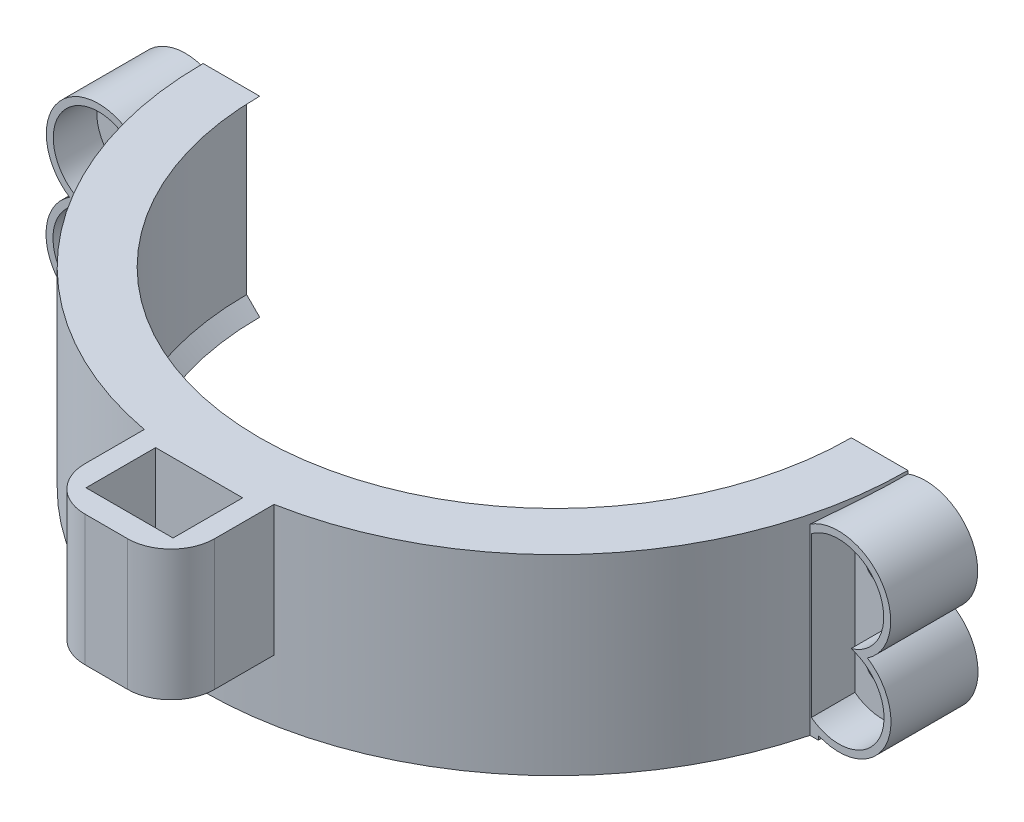
SolidWorks part; units mm, degrees
material "ABS PC"
ref_plane "Front Plane" through (0, 0, 0) normal (0, 0, 1) x (1, 0, 0)
ref_plane "Top Plane" through (0, 0, 0) normal (0, 1, 0) x (1, 0, 0)
ref_plane "Right Plane" through (0, 0, 0) normal (1, 0, 0) x (0, 0, -1)
sketch "Sketch2" plane through (0, 0, 0) normal (1, 0, 0) x (0, 0, -1)
  line L0 (0, 0) -> (-40.5, 0) construction
  line L1 (0, 0) -> (0, 11) construction
  line L24 (-34, -11) -> (-35.5, -9.5)
  line L25 (-35.5, -11) -> (-34, -11)
  line L26 (-40.5, -11) -> (-35.5, -11)
  line L27 (-40.5, 11) -> (-40.5, -11)
  line L28 (-35.5, 9.5) -> (-34, 11)
  line L29 (-35.5, -9.5) -> (-35.5, 9.5)
  line L30 (-34, 11) -> (-35.5, 11)
  line L31 (-35.5, 11) -> (-40.5, 11)
  dimension "D1" = 22
  dimension "D2" = 19
  dimension "D3" = 6.5
  dimension "D4" = 1.5
  dimension "D5" = 1.5
  dimension "D6" = 40.5
revolve "Revolve1" add sketch "Sketch2" angle 180 mid plane about L1
sketch "Sketch3" plane through (0, 0, 0) normal (0, 1, 0) x (1, 0, 0)
  line L0 (0, 0) -> (0, -51.3604) construction
  arc A2 (-40.5, 0) -> (40.5, 0) centre (0, 0) ccw
  arc A3 (-40.5, 0) -> (40.5, 0) centre (0, 0) ccw
  spline S0 degree 3 poles (40.5, 0) (41.5749, -20.6798) (31.8611, -51.1108) (0, -51.3604) knots 0 0 0 0 1 1 1 1
  spline S1 degree 3 poles (-40.5, 0) (-41.5749, -20.6798) (-31.8611, -51.1108) (0, -51.3604) knots 0 0 0 0 1 1 1 1
  dimension "D1" = 0
extrude "Boss-Extrude1" add sketch "Sketch3" against normal up to surface (11 mm away)
sketch "Sketch5" plane through (0, 0, 0) normal (0, 1, 0) x (1, 0, 0)
  line L0 (32.2986, -50) -> (-32.2986, -50)
  line L1 (0, -50) -> (0, 0) construction
  line L2 (32.2986, -50) -> (-4.5209, -70.7981)
  line L3 (-4.5209, -70.7981) -> (-32.2986, -50)
  dimension "D1" = 50
extrude "Cut-Extrude1" cut sketch "Sketch5" against normal up to next
sketch "Sketch6" plane through (0, 0, 50) normal (0, 0, 1) x (1, 0, 0)
  line L0 (-10.6698, -11) -> (10.6698, -11) construction
  line L1 (12.7, -11) -> (-12.7, -11)
  line L2 (12.7, -11) -> (12.7, 7)
  line L3 (12.7, 7) -> (-12.7, 7)
  line L4 (-12.7, -11) -> (-12.7, 7)
  line L5 (12.7, -11) -> (-12.7, 7) construction
  line L6 (12.7, 7) -> (-12.7, -11) construction
  point P0 (0, -2)
  dimension "D1" = 25.4
  dimension "D2" = 18
extrude "Boss-Extrude2" add sketch "Sketch6" against normal up to surface and the other way blind 15 up to face at (10.125, 8.25, 10.125)
sketch "Sketch8" plane through (0, 11, 0) normal (0, 1, 0) x (1, 0, 0)
  line L1 (15.1132, -40.1292) -> (15.1132, -45.0065)
  line L2 (12.7, -65) -> (12.7, -38.4572) construction
  line L3 (0, -65) -> (0, 0) construction
  line L4 (12.7, -65) -> (-12.7, -65) construction
  line L5 (-15.1132, -40.1292) -> (-15.1132, -45.0065)
  line L6 (2, -62) -> (-2, -62)
  line L7 (2, -62) -> (2, -42.1155)
  line L8 (2, -42.1155) -> (-2, -42.1155)
  line L9 (-2, -62) -> (-2, -42.1155)
  line L10 (2, -62) -> (-2, -42.1155) construction
  line L11 (2, -42.1155) -> (-2, -62) construction
  arc A0 (15.1132, -40.1292) -> (33.442, -26.8401) centre (0, 0) ccw
  arc A1 (-15.1132, -40.1292) -> (-33.442, -26.8401) centre (0, 0) cw
  spline S0 degree 3 poles (15.1132, -45.0065) (20.5532, -43.0961) (30.7451, -32.7165) (33.442, -26.8401) knots 0 0 0 0 1 1 1 1
  spline S1 degree 3 poles (-15.1132, -45.0065) (-20.5532, -43.0961) (-30.7451, -32.7165) (-33.442, -26.8401) knots 0 0 0 0 1 1 1 1
  point P1 (0, -52.0577)
  dimension "D1" = 4
  dimension "D2" = 3
extrude "Cut-Extrude3" cut sketch "Sketch8" against normal through all
fillet "Fillet1" radius 5 4 edges at (-12.7, 7, 51.7286) (12.7, 7, 51.7286) (-12.7, -2, 65) (12.7, -2, 65) first distance on face at (-12.7, -1.3333, 50.954) first distance on face at (12.7, -1.3333, 50.954)
sketch "Sketch9" plane through (0, 0, 0) normal (0, 0, 1) x (1, 0, 0)
  line L0 (40.579, -11) -> (40.5, 11) construction
  line L1 (12.7, -11) -> (40.579, -11) construction
  line L2 (40.5, 11) -> (-40.5, 11) construction
  line L3 (0, 10.25) -> (0, -10.25) construction
  arc A0 (39.2229, -0.0119) -> (45.8561, 0.0119) centre (42.5574, -5) ccw
  circle A1 centre (42.5574, -5) radius 2
  arc A2 (45.8561, 0.0119) -> (39.2229, -0.0119) centre (42.5216, 5) ccw
  circle A3 centre (42.5216, 5) radius 2
  circle A4 centre (-42.5574, -5) radius 2
  arc A5 (-39.2229, -0.0119) -> (-45.8561, 0.0119) centre (-42.5574, -5) cw
  circle A6 centre (-42.5216, 5) radius 2
  arc A7 (-45.8561, 0.0119) -> (-39.2229, -0.0119) centre (-42.5216, 5) cw
  dimension "D1" = 4
  dimension "D2" = 4
  dimension "D3" = 4
  dimension "D4" = 4
extrude "Boss-Extrude3" add sketch "Sketch9" along normal blind 10
sketch "Sketch10" plane through (0, 0, 10) normal (0, 0, 1) x (1, 0, 0)
  line L0 (39.4078, -9.1376) -> (39.4078, 9.1647)
  line L9 (0, 0) -> (0, 11.9089) construction
  line L12 (-40.9987, 0.8) -> (-40.046, 0.8)
  line L13 (-40.046, 0.8) -> (-40.046, 9.5729)
  line L14 (-40.9987, -9.9609) -> (-40.9987, 0.8)
  line L16 (-39.4078, -9.1376) -> (-39.4078, 9.1647)
  arc A0 (43.9677, 0.0051) -> (39.4078, -9.1376) centre (42.5574, -5) cw
  arc A1 (39.4078, 9.1647) -> (43.9677, 0.0051) centre (42.5216, 5) cw
  arc A8 (-40.046, 9.5729) -> (-43.9677, 0.0051) centre (-42.5216, 5) ccw
  arc A9 (-43.9677, 0.0051) -> (-40.9987, -9.9609) centre (-42.5574, -5) ccw
  arc A10 (-39.4078, 9.1647) -> (-43.9677, 0.0051) centre (-42.5216, 5) ccw
  arc A11 (-43.9677, 0.0051) -> (-39.4078, -9.1376) centre (-42.5574, -5) ccw
  dimension "D1" = 0.8
extrude "Cut-Extrude4" cut sketch "Sketch10" against normal blind 5 and the other way through all
sketch "Sketch11" plane through (0, 11, 0) normal (0, 1, 0) x (1, 0, 0)
  line L2 (48.5216, -10) -> (39.246, -10)
  line L3 (-48.5216, -10) -> (-39.246, -10)
  line L4 (40.5, 0) -> (34, 0)
  line L5 (-34, 0) -> (-40.5, 0)
  line L8 (48.5216, -10) -> (48.5216, -69.7489)
  line L9 (48.5216, -69.7489) -> (-48.5216, -69.7489)
  line L10 (-48.5216, -69.7489) -> (-48.5216, -10)
  arc A4 (-40.5, 0) -> (40.5, 0) centre (0, 0) ccw
  arc A5 (-34, 0) -> (34, 0) centre (0, 0) ccw
  arc A6 (-39.246, -10) -> (39.246, -10) centre (0, 0) ccw
  dimension "D1" = 0
extrude "Cut-Extrude5" cut sketch "Sketch11" against normal through all
sketch "Sketch12" plane through (0, 11, 0) normal (0, 1, 0) x (1, 0, 0)
  line L1 (-5, -48.9566) -> (5, -48.9566)
  line L2 (-5, -48.9566) -> (-5, -40.9566)
  line L3 (-5, -40.9566) -> (5, -40.9566)
  line L4 (5, -48.9566) -> (5, -40.9566)
  line L5 (-5, -48.9566) -> (5, -40.9566) construction
  line L6 (-5, -40.9566) -> (5, -48.9566) construction
  line L7 (-7.4558, -51.6356) -> (7.4558, -51.6356)
  line L8 (-7.4558, -51.6356) -> (-7.4558, -38.2775)
  line L9 (-7.4558, -38.2775) -> (7.4558, -38.2775)
  line L10 (7.4558, -51.6356) -> (7.4558, -38.2775)
  line L11 (-7.4558, -51.6356) -> (7.4558, -38.2775) construction
  line L12 (-7.4558, -38.2775) -> (7.4558, -51.6356) construction
  point P0 (0, -44.9566)
  point P7 (0, -44.9566)
  dimension "D1" = 8
  dimension "D2" = 10
extrude "Boss-Extrude4" add sketch "Sketch12" against normal blind 15
fillet "Fillet2" radius 5 2 edges at (-7.4558, 3.5, 51.6356) (7.4558, 3.5, 51.6356)
